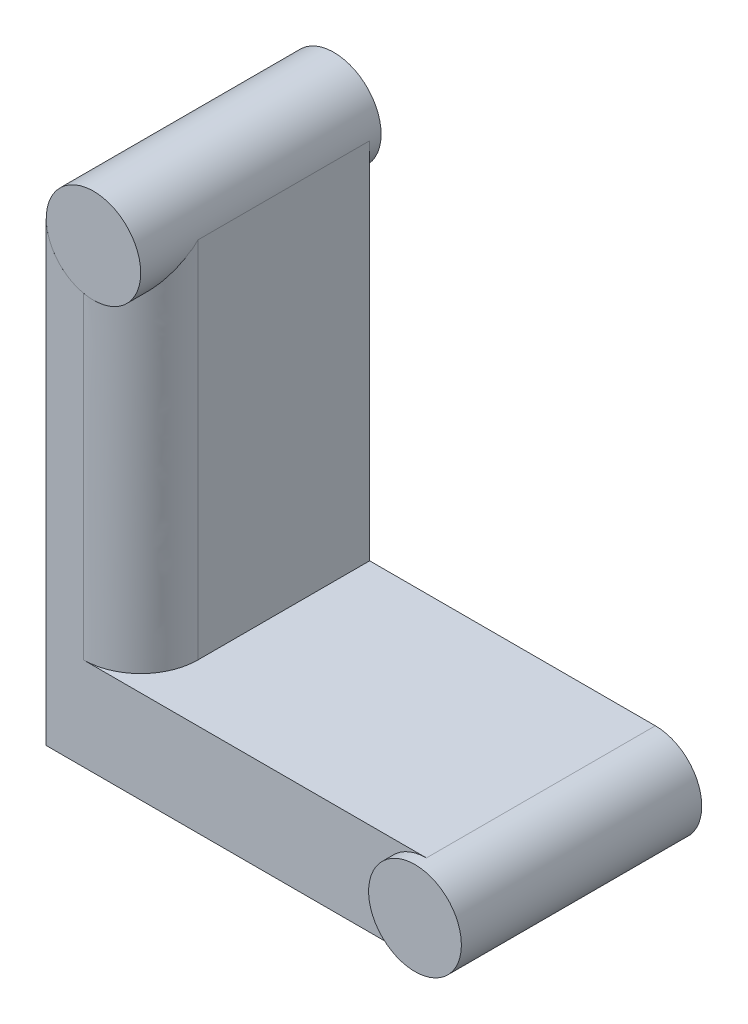
SolidWorks part; units mm, degrees
ref_plane "Front Plane" through (0, 0, 0) normal (0, 0, 1) x (1, 0, 0)
ref_plane "Top Plane" through (0, 0, 0) normal (0, 1, 0) x (1, 0, 0)
ref_plane "Right Plane" through (0, 0, 0) normal (1, 0, 0) x (0, 0, -1)
sketch "Sketch1" plane through (0, 0, 0) normal (0, 0, 1) x (1, 0, 0)
  line L0 (0, 37.4415) -> (0, -42.3308)
  line L1 (0, -42.3308) -> (66.4298, -42.3308)
  line L3 (66.4298, -26.119) -> (16.5077, -26.119)
  line L4 (16.5077, -26.119) -> (16.5077, 37.4415)
  arc A0 (0, 37.4415) -> (16.5077, 37.4415) centre (8.2539, 37.4415) ccw
  arc A1 (66.4298, -26.119) -> (66.4298, -42.3308) centre (66.4298, -34.2249) ccw
extrude "Boss-Extrude1" add sketch "Sketch1" along normal blind 40
sketch "Sketch2" plane through (0, 0, 40) normal (0, 0, 1) x (1, 0, 0)
  circle A0 centre (8.2539, 37.4415) radius 8.2539
extrude "Boss-Extrude2" add sketch "Sketch2" against normal blind 42 separate body
sketch "Sketch3" plane through (0, 0, 0) normal (0, 0, 1) x (1, 0, 0)
  circle A0 centre (66.4298, -34.2249) radius 8.1059
extrude "Boss-Extrude3" add sketch "Sketch3" along normal blind 42
fillet "Fillet4" radius 10 1 edges at (16.5077, 5.6613, 40) conic radius 10
